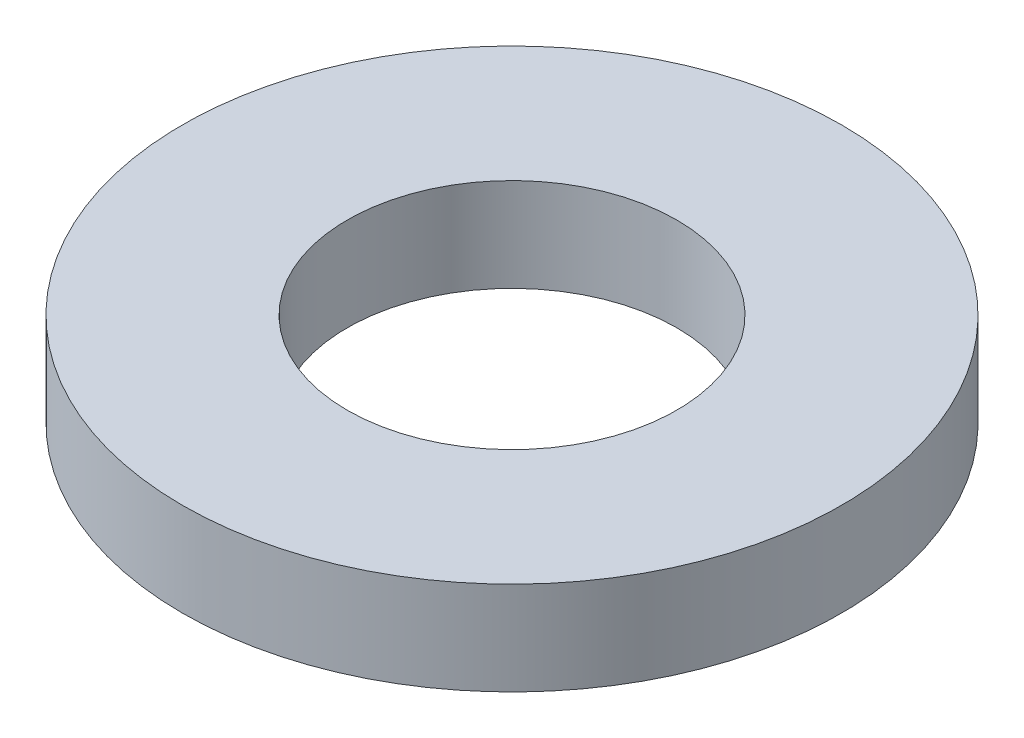
SolidWorks part; units mm, degrees
ref_plane "Front Plane" through (0, 0, 0) normal (0, 0, 1) x (1, 0, 0)
ref_plane "Top Plane" through (0, 0, 0) normal (0, 1, 0) x (1, 0, 0)
ref_plane "Right Plane" through (0, 0, 0) normal (1, 0, 0) x (0, 0, -1)
sketch "Sketch1" plane through (0, 0, 0) normal (0, 1, 0) x (1, 0, 0)
  circle A0 centre (0, 0) radius 60
  dimension "FLANGE_OD" = 120
extrude "Boss-Extrude1" add sketch "Sketch1" along normal blind 17
sketch "Sketch2" plane through (0, 0, 0) normal (0, 1, 0) x (1, 0, 0)
  circle A0 centre (0, 0) radius 30
  dimension "BORE_D" = 60
extrude "Cut-Extrude1" cut sketch "Sketch2" along normal through all
sketch "Sketch3" plane through (0, 17, 0) normal (0, 1, 0) x (1, 0, 0)
  circle A0 centre (0, 0) radius 18.433 construction
  circle A1 centre (-18.433, 0) radius 1.5127
  dimension "BOLT_D" = 3.0253
  dimension "BOLT_PCD" = 36.8659
extrude "Cut-Extrude2" cut sketch "Sketch3" against normal blind 11.0394 rebuild error yes
pattern_circular "CirPattern1" count 4 over 360 rebuild error yes
